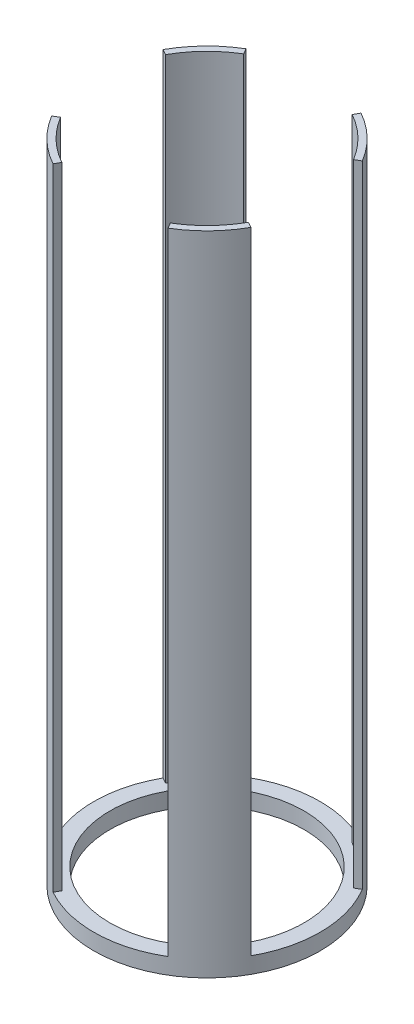
SolidWorks part; units mm, degrees
ref_plane "Front Plane" through (0, 0, 0) normal (0, 0, 1) x (1, 0, 0)
ref_plane "Top Plane" through (0, 0, 0) normal (0, 1, 0) x (1, 0, 0)
ref_plane "Right Plane" through (0, 0, 0) normal (1, 0, 0) x (0, 0, -1)
sketch "Sketch2" plane through (0, 0, 0) normal (0, 1, 0) x (1, 0, 0)
  circle A0 centre (0, 0) radius 88.9
  circle A1 centre (0, 0) radius 83.82
  dimension "D1" = 177.8
  dimension "D2" = 167.64
extrude "Boss-Extrude1" add sketch "Sketch2" along normal mid plane 508
sketch "Sketch3" plane through (0, 0, 0) normal (0, 1, 0) x (1, 0, 0)
  line L0 (0, 0) -> (169.6618, 101.6776)
  line L1 (-58.1167, 96.9749) -> (0, 0)
  line L2 (0, 0) -> (53.9, 96.9749)
  line L3 (53.9, 96.9749) -> (-58.1167, 96.9749)
  line L4 (0, 0) -> (70.9917, -118.4586)
  line L5 (70.9917, -118.4586) -> (-65.8409, -118.4586)
  line L6 (-65.8409, -118.4586) -> (0, 0)
  line L7 (169.6618, 101.6776) -> (169.6618, -94.3004)
  line L8 (169.6618, -94.3004) -> (0, 0)
  line L9 (0, 0) -> (-123.7413, 68.7771)
  line L10 (-123.7413, 68.7771) -> (-123.7413, -74.1577)
  line L11 (-123.7413, -74.1577) -> (0, 0)
  dimension "D1" = 60
  dimension "D2" = 60
  dimension "D3" = 60
  dimension "D4" = 60
  dimension "D5" = 30
  dimension "D6" = 30
extrude "Cut-Extrude1" cut sketch "Sketch3" against normal through all both and the other way through all contours L8 L7 L0 | L2 L3 L1 | L10 L11 L9 | L6 L5 L4 region at (-1.4056, 0, -64.65) region at (1.7169, 0, 78.9724) region at (113.1078, 0, -2.4591) region at (-82.4942, 0, 1.7935)
sketch "Sketch4" plane through (0, -254, 0) normal (0, -1, 0) x (1, 0, 0)
  circle A0 centre (0, 0) radius 88.9
  circle A1 centre (0, 0) radius 76.2
  dimension "D1" = 152.4
  dimension "D2" = 177.8
extrude "Boss-Extrude2" add sketch "Sketch4" against normal blind 12.7
equation "\"D1@Boss-Extrude1\"=3*12"
